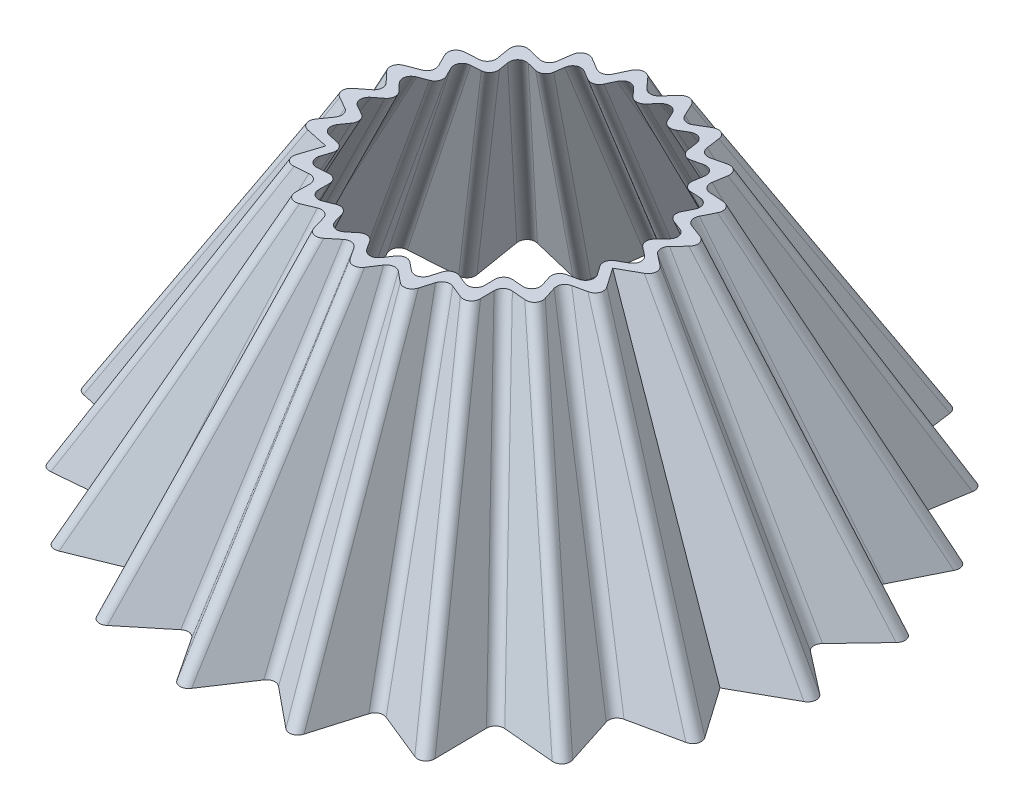
SolidWorks part; units mm, degrees
ref_plane "Front Plane" through (0, 0, 0) normal (0, 0, 1) x (1, 0, 0)
ref_plane "Top Plane" through (0, 0, 0) normal (0, 1, 0) x (1, 0, 0)
ref_plane "Right Plane" through (0, 0, 0) normal (1, 0, 0) x (0, 0, -1)
ref_plane "Plane1" through (0, 30, 0) normal (0, 1, 0) x (1, 0, 0)
sketch "Sketch1" plane through (0, 30, 0) normal (0, 1, 0) x (1, 0, 0)
  line L84 (-7.0001, 16.4745) -> (-6.2132, 24.1124)
  line L85 (-6.2132, 24.1124) -> (-1.8332, 17.8059)
  line L86 (-10.2106, 12.0981) -> (-11.5367, 18.7582)
  line L87 (-11.5367, 18.7582) -> (-6.191, 14.5703)
  line L88 (-6.191, 14.5703) -> (-5.4951, 21.3253)
  line L89 (-5.4951, 21.3253) -> (-1.6213, 15.7478)
  line L90 (-1.6213, 15.7478) -> (1.0348, 21.9976)
  line L91 (1.0348, 21.9976) -> (3.0925, 15.526)
  line L92 (3.0925, 15.526) -> (7.4728, 20.7153)
  line L93 (7.4728, 20.7153) -> (7.5315, 13.9247)
  line L94 (-1.8332, 17.8059) -> (1.1701, 24.8725)
  line L95 (1.1701, 24.8725) -> (3.4966, 17.5552)
  line L96 (3.4966, 17.5552) -> (8.4494, 23.4226)
  line L97 (8.4494, 23.4226) -> (8.5158, 15.7446)
  line L98 (8.5158, 15.7446) -> (14.9779, 19.8915)
  line L99 (14.9779, 19.8915) -> (12.7782, 12.535)
  line L100 (12.7782, 12.535) -> (20.1756, 14.5929)
  line L101 (20.1756, 14.5929) -> (15.9053, 8.2117)
  line L102 (15.9053, 8.2117) -> (23.5806, 7.9978)
  line L103 (23.5806, 7.9978) -> (17.6191, 3.1587)
  line L104 (17.6191, 3.1587) -> (24.8904, 0.6919)
  line L105 (24.8904, 0.6919) -> (17.7674, -2.175)
  line L106 (17.7674, -2.175) -> (23.9885, -6.6754)
  line L107 (23.9885, -6.6754) -> (16.3369, -7.3154)
  line L108 (16.3369, -7.3154) -> (20.9552, -13.4496)
  line L109 (20.9552, -13.4496) -> (13.4549, -11.8058)
  line L110 (13.4549, -11.8058) -> (16.0599, -19.0287)
  line L111 (16.0599, -19.0287) -> (9.3773, -15.2472)
  line L112 (9.3773, -15.2472) -> (9.7376, -22.917)
  line L113 (9.7376, -22.917) -> (4.4665, -17.3338)
  line L114 (4.4665, -17.3338) -> (2.5501, -24.7691)
  line L115 (2.5501, -24.7691) -> (-0.8411, -17.8802)
  line L116 (-0.8411, -17.8802) -> (-4.8641, -24.4203)
  line L117 (-4.8641, -24.4203) -> (-6.0741, -16.8379)
  line L118 (-6.0741, -16.8379) -> (-11.846, -21.9017)
  line L119 (-11.846, -21.9017) -> (-10.7673, -14.2995)
  line L120 (-10.7673, -14.2995) -> (-17.7753, -17.437)
  line L121 (-17.7753, -17.437) -> (-14.5038, -10.4905)
  line L122 (-14.5038, -10.4905) -> (-22.1252, -11.4229)
  line L123 (-22.1252, -11.4229) -> (-16.9515, -5.7494)
  line L124 (-16.9515, -5.7494) -> (-24.5093, -4.3939)
  line L125 (-24.5093, -4.3939) -> (-17.8931, -0.4974)
  line L126 (-17.8931, -0.4974) -> (-24.7155, 3.0255)
  line L127 (-24.7155, 3.0255) -> (-17.2448, 4.7988)
  line L128 (-17.2448, 4.7988) -> (-22.7257, 10.1761)
  line L129 (-22.7257, 10.1761) -> (-15.0642, 9.6686)
  line L130 (-15.0642, 9.6686) -> (-18.7166, 16.4225)
  line L131 (-18.7166, 16.4225) -> (-11.545, 13.6793)
  line L132 (-11.545, 13.6793) -> (-13.0444, 21.2097)
  line L133 (-13.0444, 21.2097) -> (-7.0001, 16.4745)
  line L134 (7.5315, 13.9247) -> (13.2467, 17.5923)
  line L135 (13.2467, 17.5923) -> (11.3013, 11.0861)
  line L136 (11.3013, 11.0861) -> (17.8436, 12.9062)
  line L137 (17.8436, 12.9062) -> (14.0669, 7.2625)
  line L138 (14.0669, 7.2625) -> (20.855, 7.0733)
  line L139 (20.855, 7.0733) -> (15.5826, 2.7936)
  line L140 (15.5826, 2.7936) -> (22.0134, 0.6119)
  line L141 (22.0134, 0.6119) -> (15.7137, -1.9236)
  line L142 (15.7137, -1.9236) -> (21.2158, -5.9038)
  line L143 (21.2158, -5.9038) -> (14.4486, -6.4698)
  line L144 (14.4486, -6.4698) -> (18.5331, -11.895)
  line L145 (18.5331, -11.895) -> (11.8997, -10.4412)
  line L146 (11.8997, -10.4412) -> (14.2036, -16.8292)
  line L147 (14.2036, -16.8292) -> (8.2934, -13.4848)
  line L148 (8.2934, -13.4848) -> (8.6121, -20.2681)
  line L149 (8.6121, -20.2681) -> (3.9503, -15.3303)
  line L150 (3.9503, -15.3303) -> (2.2553, -21.9061)
  line L151 (2.2553, -21.9061) -> (-0.7439, -15.8135)
  line L152 (-0.7439, -15.8135) -> (-4.3018, -21.5977)
  line L153 (-4.3018, -21.5977) -> (-5.372, -14.8917)
  line L154 (-5.372, -14.8917) -> (-10.4767, -19.3702)
  line L155 (-10.4767, -19.3702) -> (-9.5227, -12.6467)
  line L156 (-9.5227, -12.6467) -> (-15.7207, -15.4215)
  line L157 (-15.7207, -15.4215) -> (-12.8273, -9.278)
  line L158 (-12.8273, -9.278) -> (-19.5679, -10.1026)
  line L159 (-19.5679, -10.1026) -> (-14.9922, -5.0848)
  line L160 (-14.9922, -5.0848) -> (-21.6763, -3.886)
  line L161 (-21.6763, -3.886) -> (-15.8249, -0.4399)
  line L162 (-15.8249, -0.4399) -> (-21.8587, 2.6758)
  line L163 (-21.8587, 2.6758) -> (-15.2515, 4.2441)
  line L164 (-15.2515, 4.2441) -> (-20.0989, 8.9999)
  line L165 (-20.0989, 8.9999) -> (-13.323, 8.551)
  line L166 (-13.323, 8.551) -> (-16.5532, 14.5243)
  line L167 (-16.5532, 14.5243) -> (-10.2106, 12.0981)
  circle A22 centre (0, 0) radius 24.9 construction
  circle A23 centre (0, 0) radius 17.9 construction
  circle A24 centre (0, 0) radius 17.9
  circle A25 centre (0, 0) radius 17.9
  circle A26 centre (0, 0) radius 17.9
  circle A27 centre (0, 0) radius 17.9
  circle A28 centre (0, 0) radius 17.9
  circle A29 centre (0, 0) radius 17.9
  circle A30 centre (0, 0) radius 17.9
  circle A31 centre (0, 0) radius 17.9
  circle A32 centre (0, 0) radius 17.9
  circle A33 centre (0, 0) radius 17.9
  circle A34 centre (0, 0) radius 17.9
  circle A35 centre (0, 0) radius 17.9
  circle A36 centre (0, 0) radius 17.9
  circle A37 centre (0, 0) radius 17.9
  circle A38 centre (0, 0) radius 17.9
  circle A39 centre (0, 0) radius 17.9
  circle A40 centre (0, 0) radius 17.9
  circle A41 centre (0, 0) radius 17.9
  circle A42 centre (0, 0) radius 17.9
  circle A43 centre (0, 0) radius 17.9
  dimension "D1" = 49.8
  dimension "D2" = 1
sketch "Sketch2" plane through (0, 0, 0) normal (0, 1, 0) x (1, 0, 0)
  line L0 (-8.8427, 28.6672) -> (-5.4251, 35.9934)
  line L1 (-5.4251, 35.9934) -> (0, 30)
  line L2 (5.4251, 35.9934) -> (8.8427, 28.6672)
  line L3 (0, 30) -> (5.4251, 35.9934)
  line L4 (15.7934, 32.7953) -> (16.8996, 24.7872)
  line L5 (8.8427, 28.6672) -> (15.7934, 32.7953)
  line L6 (24.7583, 26.6831) -> (23.4549, 18.7047)
  line L7 (16.8996, 24.7872) -> (24.7583, 26.6831)
  line L8 (31.5233, 18.2) -> (27.9262, 10.9602)
  line L9 (23.4549, 18.7047) -> (31.5233, 18.2)
  line L10 (35.4874, 8.0998) -> (29.9161, 2.2419)
  line L11 (27.9262, 10.9602) -> (35.4874, 8.0998)
  line L12 (36.2982, -2.7202) -> (29.2478, -6.6756)
  line L13 (29.9161, 2.2419) -> (36.2982, -2.7202)
  line L14 (33.8838, -13.2984) -> (25.9808, -15)
  line L15 (29.2478, -6.6756) -> (33.8838, -13.2984)
  line L16 (28.4587, -22.695) -> (20.4052, -21.9916)
  line L17 (25.9808, -15) -> (28.4587, -22.695)
  line L18 (20.5049, -30.0751) -> (13.0165, -27.0291)
  line L19 (20.4052, -21.9916) -> (20.5049, -30.0751)
  line L20 (10.7291, -34.7829) -> (4.4713, -29.6649)
  line L21 (13.0165, -27.0291) -> (10.7291, -34.7829)
  line L22 (0, -36.4) -> (-4.4713, -29.6649)
  line L23 (4.4713, -29.6649) -> (0, -36.4)
  line L24 (-10.7291, -34.7829) -> (-13.0165, -27.0291)
  line L25 (-4.4713, -29.6649) -> (-10.7291, -34.7829)
  line L26 (-20.5049, -30.0751) -> (-20.4052, -21.9916)
  line L27 (-13.0165, -27.0291) -> (-20.5049, -30.0751)
  line L28 (-28.4587, -22.695) -> (-25.9808, -15)
  line L29 (-20.4052, -21.9916) -> (-28.4587, -22.695)
  line L30 (-33.8838, -13.2984) -> (-29.2478, -6.6756)
  line L31 (-25.9808, -15) -> (-33.8838, -13.2984)
  line L32 (-36.2982, -2.7202) -> (-29.9161, 2.2419)
  line L33 (-29.2478, -6.6756) -> (-36.2982, -2.7202)
  line L34 (-35.4874, 8.0998) -> (-27.9262, 10.9602)
  line L35 (-29.9161, 2.2419) -> (-35.4874, 8.0998)
  line L36 (-31.5233, 18.2) -> (-23.4549, 18.7047)
  line L37 (-27.9262, 10.9602) -> (-31.5233, 18.2)
  line L38 (-24.7583, 26.6831) -> (-16.8996, 24.7872)
  line L39 (-23.4549, 18.7047) -> (-24.7583, 26.6831)
  line L40 (-15.7934, 32.7953) -> (-8.8427, 28.6672)
  line L41 (-16.8996, 24.7872) -> (-15.7934, 32.7953)
  line L42 (-29.9575, 17.296) -> (-22.2899, 17.7756)
  line L43 (-22.2899, 17.7756) -> (-23.5285, 25.3577)
  line L44 (-23.5285, 25.3577) -> (-16.0602, 23.556)
  line L45 (-16.0602, 23.556) -> (-15.0089, 31.1663)
  line L46 (-15.0089, 31.1663) -> (-8.4034, 27.2433)
  line L47 (-8.4034, 27.2433) -> (-5.1557, 34.2056)
  line L48 (-5.1557, 34.2056) -> (0, 28.5099)
  line L49 (0, 28.5099) -> (5.1557, 34.2056)
  line L50 (5.1557, 34.2056) -> (8.4034, 27.2433)
  line L51 (8.4034, 27.2433) -> (15.0089, 31.1663)
  line L52 (15.0089, 31.1663) -> (16.0602, 23.556)
  line L53 (16.0602, 23.556) -> (23.5285, 25.3577)
  line L54 (23.5285, 25.3577) -> (22.2899, 17.7756)
  line L55 (22.2899, 17.7756) -> (29.9575, 17.296)
  line L56 (29.9575, 17.296) -> (26.5391, 10.4158)
  line L57 (26.5391, 10.4158) -> (33.7247, 7.6974)
  line L58 (33.7247, 7.6974) -> (28.4302, 2.1305)
  line L59 (28.4302, 2.1305) -> (34.4953, -2.5851)
  line L60 (34.4953, -2.5851) -> (27.7951, -6.344)
  line L61 (27.7951, -6.344) -> (32.2008, -12.6379)
  line L62 (32.2008, -12.6379) -> (24.6903, -14.2549)
  line L63 (24.6903, -14.2549) -> (27.0451, -21.5677)
  line L64 (27.0451, -21.5677) -> (19.3916, -20.8992)
  line L65 (19.3916, -20.8992) -> (19.4864, -28.5812)
  line L66 (19.4864, -28.5812) -> (12.37, -25.6865)
  line L67 (12.37, -25.6865) -> (10.1962, -33.0552)
  line L68 (10.1962, -33.0552) -> (4.2492, -28.1914)
  line L69 (4.2492, -28.1914) -> (0, -34.592)
  line L70 (0, -34.592) -> (-4.2492, -28.1914)
  line L71 (-4.2492, -28.1914) -> (-10.1962, -33.0552)
  line L72 (-10.1962, -33.0552) -> (-12.37, -25.6865)
  line L73 (-12.37, -25.6865) -> (-19.4864, -28.5812)
  line L74 (-19.4864, -28.5812) -> (-19.3916, -20.8992)
  line L75 (-19.3916, -20.8992) -> (-27.0451, -21.5677)
  line L76 (-27.0451, -21.5677) -> (-24.6903, -14.2549)
  line L77 (-24.6903, -14.2549) -> (-32.2008, -12.6379)
  line L78 (-32.2008, -12.6379) -> (-27.7951, -6.344)
  line L79 (-27.7951, -6.344) -> (-34.4953, -2.5851)
  line L80 (-34.4953, -2.5851) -> (-28.4302, 2.1305)
  line L81 (-28.4302, 2.1305) -> (-33.7247, 7.6974)
  line L82 (-33.7247, 7.6974) -> (-26.5391, 10.4158)
  line L83 (-26.5391, 10.4158) -> (-29.9575, 17.296)
  circle A0 centre (0, 0) radius 36.4
  circle A1 centre (0, 0) radius 28.5099
  point P67 (-4.686, -14.0714)
  dimension "D1" = 57.0197
  dimension "D2" = 72.8
  dimension "D3" = 1
extrude "Boss-Extrude1" add sketch "Sketch2" along normal blind 30 draft 19 contours L25 L24 L27 L26 L29 L28 L31 L30 L33 L32 L35 L34 L37 L36 L39 L38 L41 L40 L0 L1 L3 L2 L5 L4 L7 L6 L9 L8 L11 L10 L13 L12 L15 L14 L17 L16 L19 L18 L21 L20 L23 L22
extrude "Cut-Extrude1" cut sketch "Sketch2<6>" along normal blind 30 draft 19 contours L68 L69 L70 L71 L72 L73 L74 L75 L76 L77 L78 L79 L80 L81 L82 L83 L42 L43 L44 L45 L46 L47 L48 L49 L50 L51 L52 L53 L54 L55 L56 L57 L58 L59 L60 L61 L62 L63 L64 L65 L66 L67
sketch "Sketch2<6>" plane through (0, 0, 0) normal (0, 1, 0) x (1, 0, 0) same geometry as "Sketch2"
fillet "Fillet1" radius 1 43 edges at (3.3242, 15, 22.0545) (9.6772, 15, 20.0949) (15.1703, 15, 16.3497) (19.3155, 15, 11.1518) (20.2917, 15, 4.6314) (22.2413, 15, -1.6668) (20.7619, 15, -8.1484) (17.4377, 15, -13.9061) (12.5641, 15, -18.4281) (6.5741, 15, -21.3127) (0, 15, -22.3036) (-6.5741, 15, -21.3127) (-12.5641, 15, -18.4281) (-17.4377, 15, -13.9061) (-20.7619, 15, -8.1484) (-22.2413, 15, -1.6668) (-21.7444, 15, 4.963) (-18.025, 15, 10.4067) (-15.1703, 15, 16.3497) (-9.6772, 15, 20.0949) (-3.3242, 15, 22.0545) (-7.9766, 15, 25.8594) (0, 15, 27.0617) (7.9766, 15, 25.8594) (15.2444, 15, 22.3594) (21.1577, 15, 16.8727) (25.191, 15, 9.8868) (26.9861, 15, 2.0223) (26.3832, 15, -6.0218) (23.4361, 15, -13.5309) (18.4066, 15, -19.8376) (11.7416, 15, -24.3818) (4.0333, 15, -26.7595) (-4.0333, 15, -26.7595) (-11.7416, 15, -24.3818) (-17.1769, 15, -18.5123) (-23.4361, 15, -13.5309) (-26.3832, 15, -6.0218) (-26.9861, 15, 2.0223) (-25.191, 15, 9.8868) (-21.1577, 15, 16.8727) (-15.2444, 15, 22.3594) (-18.4066, 15, -19.8376)
fillet "Fillet2" radius 1 39 edges at (0, 15, 25.2537) (-3.1021, 15, 20.581) (-7.4437, 15, 24.1318) (-9.0306, 15, 18.7523) (-14.2259, 15, 20.8656) (-14.1568, 15, 15.2574) (-19.7441, 15, 15.7454) (-23.508, 15, 9.2262) (-20.2917, 15, 4.6314) (-25.1831, 15, 1.8872) (-20.7553, 15, -1.5554) (-24.6205, 15, -5.6195) (-19.3747, 15, -7.604) (-21.8703, 15, -12.6269) (-16.2726, 15, -12.977) (-11.7247, 15, -17.1969) (-10.9572, 15, -22.7528) (-6.1349, 15, -19.8888) (-3.7639, 15, -24.9716) (0, 15, -20.8135) (3.7639, 15, -24.9716) (6.1349, 15, -19.8888) (23.508, 15, 9.2262) (10.9572, 15, -22.7528) (11.7247, 15, -17.1969) (17.1769, 15, -18.5123) (16.2726, 15, -12.977) (21.8703, 15, -12.6269) (19.3747, 15, -7.604) (25.1831, 15, 1.8872) (24.6205, 15, -5.6195) (20.7553, 15, -1.5554) (18.025, 15, 10.4067) (14.1568, 15, 15.2574) (19.7441, 15, 15.7454) (14.2259, 15, 20.8656) (9.0306, 15, 18.7523) (7.4437, 15, 24.1318) (3.1021, 15, 20.581)
